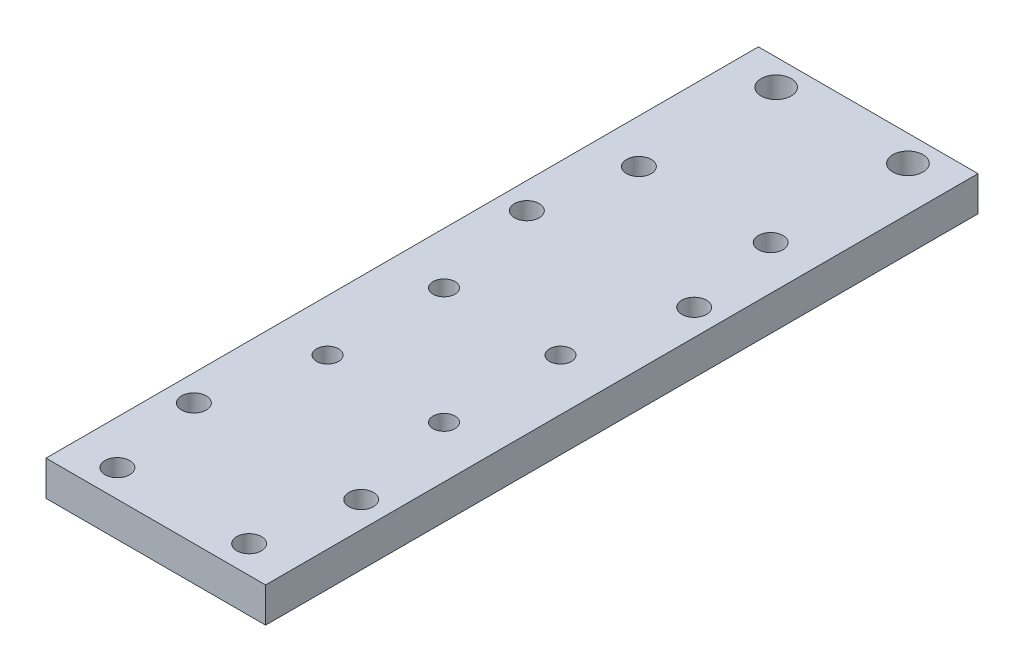
SolidWorks part; units mm, degrees
material "6061 Alloy"
ref_plane "Front Plane" through (0, 0, 0) normal (0, 0, 1) x (1, 0, 0)
ref_plane "Top Plane" through (0, 0, 0) normal (0, 1, 0) x (1, 0, 0)
ref_plane "Right Plane" through (0, 0, 0) normal (1, 0, 0) x (0, 0, -1)
sketch "Sketch1" plane through (0, 0, 0) normal (0, 1, 0) x (1, 0, 0)
  line L1 (-20, 80) -> (20, 80)
  line L2 (-20, 80) -> (-20, -80)
  line L3 (-20, -80) -> (20, -80)
  line L4 (20, 80) -> (20, -80)
  line L5 (0, -80) -> (0, 80) construction
  line L6 (-20, 0) -> (20, 0) construction
  point P0 (0, 0)
  dimension "D1" = 40
  dimension "D2" = 160
extrude "Boss-Extrude1" add sketch "Sketch1" along normal mid plane 6.35
sketch "Sketch3" plane through (0, 0, 0) normal (0, 1, 0) x (1, 0, 0)
  line L0 (0, 75.2375) -> (12, 75.2375) construction
  line L5 (0, -80) -> (0, 80) construction
  line L6 (-20, 0) -> (20, 0) construction
  line L7 (0, 50.2375) -> (12, 50.2375) construction
  line L8 (20, 80) -> (-20, 80) construction
  line L9 (-20, 80) -> (-20, -80) construction
  line L10 (-20, -80) -> (20, -80) construction
  line L11 (20, -80) -> (20, 80) construction
  circle A0 centre (12, 75.2375) radius 2.75
  circle A1 centre (12, 50.2375) radius 2.25
  circle A2 centre (-12, 50.2375) radius 2.25
  circle A3 centre (-12, 75.2375) radius 2.75
  circle A4 centre (-12, -44.7625) radius 2.25
  circle A5 centre (12, -44.7625) radius 2.25
  point P0 (0, 0)
  dimension "D4" = 5.5
  dimension "D5" = 4.5
  dimension "D1" = 4.7625
  dimension "D2" = 25
  dimension "D3" = 12
  dimension "D6" = 2
extrude "M4/5_through" cut sketch "Sketch3" against normal up to surface (3.175 mm away) and the other way blind 6.35 up to face at (0, -3.175, 0)
sketch "Sketch4" plane through (0, 0, -80) normal (0, 0, -1) x (-1, 0, 0)
  circle A0 centre (0, 0) radius 1.5
  dimension "D1" = 3
extrude "M3_DRILL" cut sketch "Sketch4" against normal blind 8
sketch "Sketch5" plane through (0, 3.175, 0) normal (0, 1, 0) x (1, 0, 0)
  line L0 (-12, -44.7625) -> (0, -44.7625) construction
  line L2 (0, 0) -> (0, -23.6676) construction
  line L3 (-12, 50.2375) -> (-12, -44.7625) construction
  line L4 (-12, 2.7375) -> (-1.1233, 2.7375) construction
  line L5 (-20, 80) -> (-20, -80) construction
  circle A0 centre (-15.2375, -27.5875) radius 2.25
  circle A1 centre (15.2375, -27.5875) radius 2.25
  circle A2 centre (15.2375, 33.0625) radius 2.25
  circle A3 centre (-15.2375, 33.0625) radius 2.25
  circle A4 centre (-12, -44.7625) radius 2.25 construction
  dimension "D2" = 4.5
  dimension "D1" = 17.175
  dimension "D3" = 4.7625
extrude "M4_through" cut sketch "Sketch5" against normal up to surface (6.35 mm away) up to face at (12, -3.175, 47.0125)
sketch "Sketch6" plane through (0, 0, 0) normal (0, 1, 0) x (1, 0, 0)
  line L0 (0, 2.7375) -> (0, 0) construction
  line L1 (-10.6066, 13.3441) -> (0, 2.7375) construction
  line L2 (-15.2375, 33.0625) -> (-15.2375, -27.5875) construction
  line L3 (-15.2375, 2.7375) -> (0, 2.7375) construction
  circle A0 centre (0, 2.7375) radius 15 construction
  circle A1 centre (-10.6066, 13.3441) radius 2
  circle A2 centre (10.6066, 13.3441) radius 2
  circle A3 centre (10.6066, -7.8691) radius 2
  circle A4 centre (-10.6066, -7.8691) radius 2
  point P15 (0, 2.7375)
  point P18 (0, 7.9524)
  point P19 (0, 2.7375)
  dimension "D2" = 30
  dimension "D4" = 4
  dimension "D3" = 135
  dimension "D5" = 4
extrude "M4_Drill" cut sketch "Sketch6" along normal up to surface (3.175 mm away) and the other way blind 10 up to face at (-15.2375, 3.175, -35.3125)
sketch "Sketch7" plane through (0, 3.175, 0) normal (0, 1, 0) x (1, 0, 0)
  line L0 (-12, -44.7625) -> (12, -44.7625) construction
  line L1 (20, -80) -> (20, 80) construction
  line L2 (-20, -80) -> (20, -80)
  line L3 (-20, -80) -> (-20, -49.7625)
  line L4 (-20, -49.7625) -> (20, -49.7625)
  line L5 (20, -80) -> (20, -49.7625)
  line L6 (0, -49.7625) -> (0, -80) construction
  line L7 (-20, -64.8812) -> (20, -64.8812) construction
  point P216 (0, -64.8812)
  dimension "D1" = 5
extrude "Cut-Extrude2" cut sketch "Sketch7" against normal up to surface (6.35 mm away) up to face at (-10.6066, -3.175, 9.8691)
